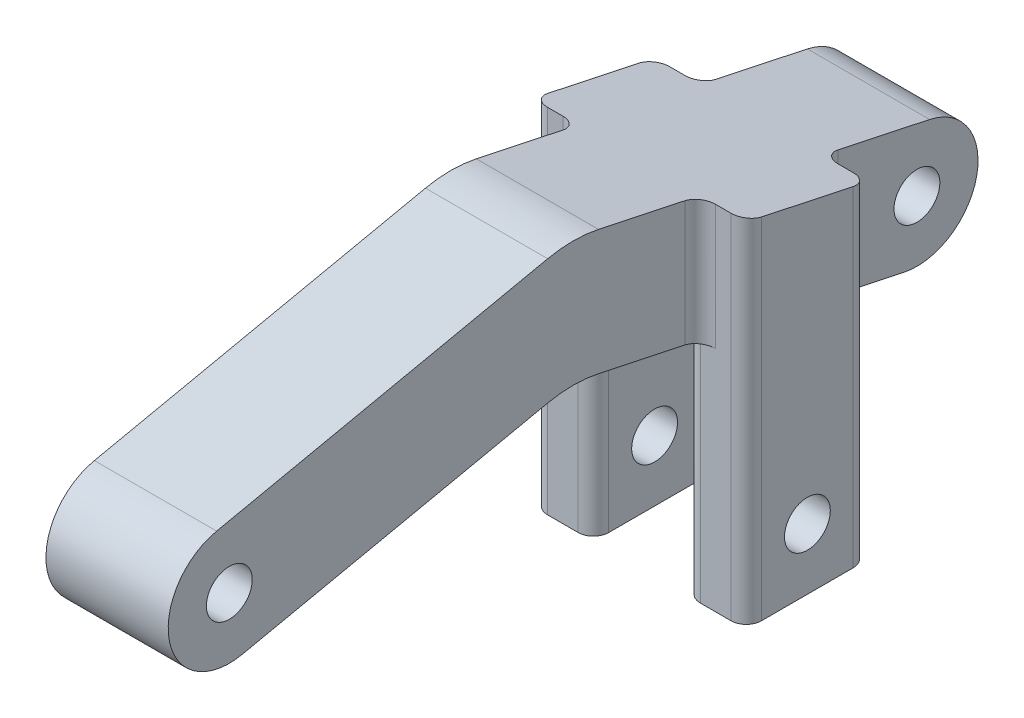
SolidWorks part; units mm, degrees
ref_plane "Alzado" through (0, 0, 0) normal (0, 0, 1) x (1, 0, 0)
ref_plane "Planta" through (0, 0, 0) normal (0, 1, 0) x (1, 0, 0)
ref_plane "Vista lateral" through (0, 0, 0) normal (1, 0, 0) x (0, 0, -1)
sketch "Croquis1" plane through (0, 0, 0) normal (1, 0, 0) x (0, 0, -1)
  line L0 (-23.3316, 3.9126) -> (0, 8.8719) construction
  line L9 (0, 8.8719) -> (23.3316, 3.9126) construction
  line L10 (-21.6684, -3.9126) -> (0, 0.6932) construction
  line L15 (-22.5, 0) -> (22.5, 0) construction
  line L16 (0, 0.6932) -> (21.6684, -3.9126) construction
  line L17 (-23.3316, 3.9126) -> (-1.6633, 8.5183)
  line L18 (1.6633, 8.5183) -> (23.3316, 3.9126)
  line L19 (-21.6684, -3.9126) -> (-1.6633, 0.3396)
  line L20 (1.6633, 0.3396) -> (21.6684, -3.9126)
  circle A2 centre (-22.5, 0) radius 1.5
  circle A4 centre (22.5, 0) radius 1.5
  arc A7 (-23.3316, 3.9126) -> (-21.6684, -3.9126) centre (-22.5, 0) ccw
  arc A8 (21.6684, -3.9126) -> (23.3316, 3.9126) centre (22.5, 0) ccw
  arc A9 (-1.6633, 8.5183) -> (1.6633, 8.5183) centre (0, 0.6932) cw
  arc A10 (-1.6633, 0.3396) -> (1.6633, 0.3396) centre (0, -7.4856) cw
  point P0 (0, 0)
  point P1 (0, 0)
  dimension "D4" = 3
  dimension "D2" = 8
  dimension "D5" = 8
  dimension "D1" = 45
  dimension "D3" = 12
  dimension "D7" = 12
extrude "Saliente-Extruir1" add sketch "Croquis1" along normal mid plane 8
sketch "Croquis3" plane through (0, 0, 0) normal (0, 1, 0) x (1, 0, 0)
  line L1 (4, 23.3316) -> (-4, 23.3316) construction
  line L2 (-4, 16.3316) -> (-7, 16.3316)
  line L3 (-4, 16.3316) -> (-4, 8.3316)
  line L4 (-4, 8.3316) -> (-7, 8.3316)
  line L5 (-7, 16.3316) -> (-7, 8.3316)
  line L10 (0, 0) -> (0, 23.3316) construction
  line L13 (4, 8.3316) -> (7, 8.3316)
  line L14 (7, 16.3316) -> (7, 8.3316)
  line L15 (4, 16.3316) -> (7, 16.3316)
  line L16 (4, 16.3316) -> (4, 8.3316)
  line L17 (-4, 23.3316) -> (-4, 1.6633) construction
  point P10 (-7, 12.3316)
  point P11 (-4, 12.3316)
  dimension "D1" = 3
  dimension "D2" = 8
  dimension "D3" = 7
extrude "Saliente-Extruir2" add sketch "Croquis3" against normal up to surface and the other way up to surface up to face at (0, -1.7865, -11.6658) other way up to face at (0, 6.2155, -12.4975)
sketch "Croquis4" plane through (0, 0, 0) normal (0, -1, 0) x (1, 0, 0)
  line L25 (-7, -8.3316) -> (7, -8.3316)
  line L26 (-7, -8.3316) -> (-7, -16.3316)
  line L27 (-7, -16.3316) -> (7, -16.3316)
  line L28 (7, -8.3316) -> (7, -16.3316)
extrude "Saliente-Extruir3" add sketch "Croquis4" along normal blind 16
sketch "Croquis7" plane through (0, -16, 0) normal (0, -1, 0) x (1, 0, 0)
  line L1 (3, -16.3316) -> (-3, -16.3316)
  line L2 (3, -16.3316) -> (3, -8.3316)
  line L3 (3, -8.3316) -> (-3, -8.3316)
  line L4 (-3, -16.3316) -> (-3, -8.3316)
  line L5 (3, -16.3316) -> (-3, -8.3316) construction
  line L6 (3, -8.3316) -> (-3, -16.3316) construction
  line L8 (4, -8.3316) -> (-4, -8.3316) construction
  line L9 (-7, -16.3316) -> (7, -16.3316) construction
  point P0 (0, -12.3316)
  dimension "D1" = 6
extrude "Cortar-Extruir2" cut sketch "Croquis7" against normal up to surface (13.2218 mm away) up to face at (0, -0.3691, -4.9975)
fillet "Redondeo1" radius 1 12 edges at (4, 3.0116, -8.3316) (4, 1.3111, -16.3316) (-4, 3.0116, -8.3316) (-4, 1.3111, -16.3316) (3, -9.3891, -16.3316) (-3, -9.3891, -16.3316) (-3, -8.5389, -8.3316) (3, -8.5389, -8.3316) (7, -4.4495, -8.3316) (7, -5.2998, -16.3316) (-7, -5.2998, -16.3316) (-7, -4.4495, -8.3316)
sketch "Croquis6" plane through (0, 0, 0) normal (1, 0, 0) x (0, 0, -1)
  line L1 (15.3316, -16) -> (9.3316, -16) construction
  circle A0 centre (12.3316, -12) radius 1.5
  point P8 (12.3316, -16)
  dimension "D2" = 3
  dimension "D1" = 12
extrude "Cortar-Extruir1" cut sketch "Croquis6" against normal through all both and the other way through all
